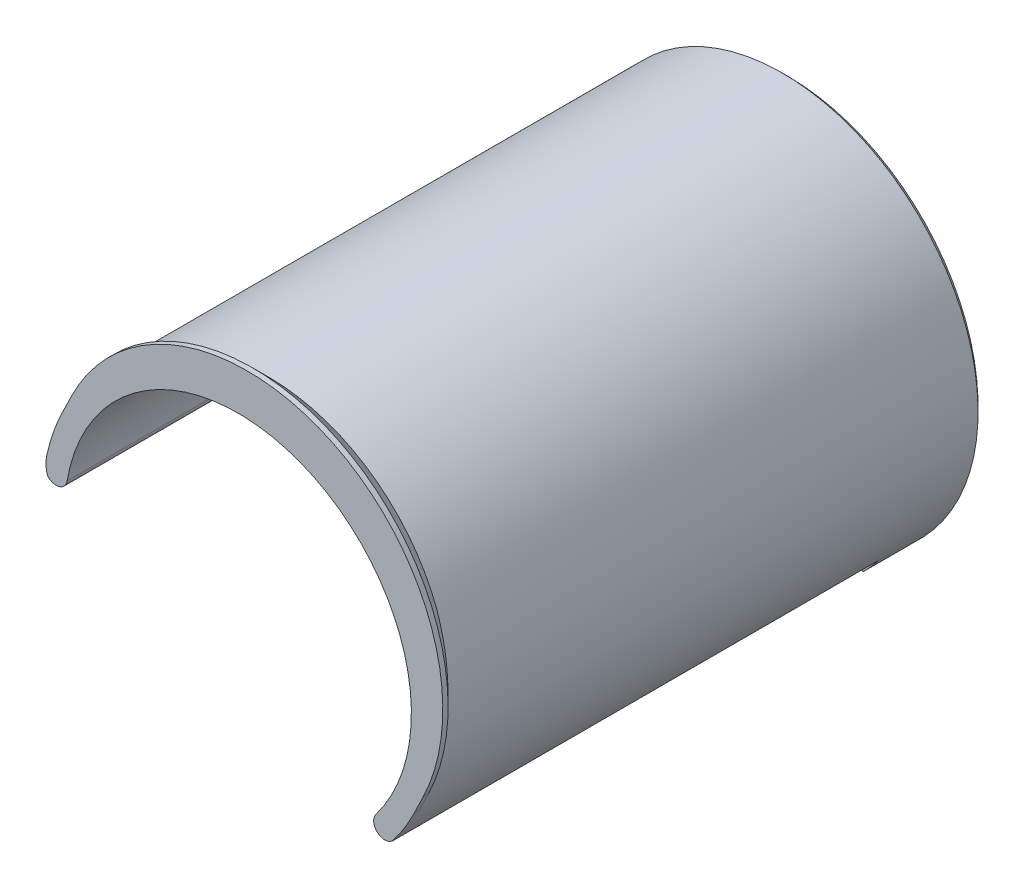
SolidWorks part; units mm, degrees
ref_plane "Front Plane" through (0, 0, 0) normal (0, 0, 1) x (1, 0, 0)
ref_plane "Top Plane" through (0, 0, 0) normal (0, 1, 0) x (1, 0, 0)
ref_plane "Right Plane" through (0, 0, 0) normal (1, 0, 0) x (0, 0, -1)
sketch "Sketch1" plane through (0, 0, 0) normal (0, 0, 1) x (1, 0, 0)
  line L0 (0, 0) -> (2.4655, -2.0399) construction
  line L1 (0, -72.4563) -> (0, 0) construction
  line L2 (-24.9525, 0) -> (63.5919, 0) construction
  line L5 (-4.4616, 0) -> (-3.2, 0)
  line L7 (2.4655, -2.0399) -> (17.7098, -14.6529)
  arc A0 (21.6843, -14.7364) -> (-7.5908, 3.8693) centre (10.5, 0) ccw
  arc A1 (-3.2, 0) -> (2.4655, -2.0399) centre (0, 0) ccw
  arc A2 (17.7098, -14.6529) -> (21.6843, -14.7364) centre (19.7497, -12.1874) ccw
  circle A3 centre (19.7497, -12.1874) radius 1.6
  arc A4 (-4.4616, 0) -> (-7.5908, 3.8693) centre (-4.4616, 3.2) cw
  circle A9 centre (0, 0) radius 1.6
  dimension "D1" = 3.2
  dimension "D3" = 10.5
  dimension "D5" = 3.2
  dimension "D6" = 37
  dimension "D7" = 39.604
extrude "Boss-Extrude1" add sketch "Sketch1" along normal blind 52
sketch "Sketch2" plane through (0, 0, 52) normal (0, 0, 1) x (1, 0, 0)
  line L0 (-7.7522, 2.9303) -> (-10.2673, 3.3341)
  line L1 (25.098, -11.3414) -> (27.1096, -12.9043)
  arc A0 (23.5461, -9.9377) -> (-5.6671, 2.754) centre (10.5, 0) ccw
  arc A1 (21.6843, -14.7364) -> (-7.5908, 3.8693) centre (10.5, 0) ccw construction
  arc A2 (23.5461, -9.9377) -> (25.098, -11.3414) centre (24.3814, -10.574) ccw
  arc A3 (-7.7522, 2.9303) -> (-5.6671, 2.754) centre (-6.7022, 2.9303) ccw
  arc A4 (-7.7522, 2.9303) -> (25.098, -11.3414) centre (10.5, 0) ccw construction
  arc A5 (-10.2673, 3.3341) -> (27.1096, -12.9043) centre (10.5, 0) ccw
  dimension "D1" = 2.1
extrude "Cut-Extrude1" cut sketch "Sketch2" against normal offset from surface (46 mm away) 6 up to face at (21.3497, -12.1874, 0)
sketch "Sketch3" plane through (0, 0, 6) normal (0, 0, 1) x (1, 0, 0)
  line L0 (1.6921, 2.716) -> (20.4366, -8.962)
  arc A1 (1.6921, 2.716) -> (-0.5483, 3.1527) centre (0, 0) ccw
  circle A2 centre (19.7497, -12.1874) radius 3.2 construction
  arc A3 (-3.908, 7.8339) -> (-0.5483, 3.1527) centre (-1.0967, 6.3053) ccw
  arc A4 (20.4366, -8.962) -> (24.9478, -7.7602) centre (22.1287, -6.246) ccw
  arc A6 (24.9478, -7.7602) -> (-3.908, 7.8339) centre (10.5, 0) ccw
extrude "Cut-Extrude2" cut sketch "Sketch3" against normal offset from surface (3.6 mm away) 2.4 up to face at (21.3497, -12.1874, 0)
chamfer "Chamfer1" distance 3 angle 45 5 edges at (18.2971, 14.428, 2.4) (22.9525, -9.3381, 2.4) (11.0644, -3.123, 2.4) (0.6121, 3.1409, 2.4) (-3.6964, 4.4395, 2.4)
chamfer "Chamfer2" distance 0.5 angle 45 8 edges at (1.6, 0, 0) (-3.8308, 0, 0) (-1.0841, -3.0108, 0) (10.0877, -8.3464, 0) (19.6825, -15.3867, 0) (20.4231, 15.6135, 0) (-6.9498, 1.1877, 0) (21.3497, -12.1874, 0)
sketch "Sketch4" plane through (0, 0, 52) normal (0, 0, 1) x (1, 0, 0)
  line L0 (-6.1477, 8.0687) -> (-5.2754, 9.8684)
  line L1 (27.1477, -8.0687) -> (28.02, -6.2689)
  line L2 (-6.1477, 8.0687) -> (-4.258, 7.1528)
  line L3 (25.258, -7.1528) -> (27.1477, -8.0687)
  arc A0 (28.02, -6.2689) -> (-5.2754, 9.8684) centre (11.3723, 1.7998) ccw
  arc A1 (25.1091, -11.3501) -> (-7.5908, 3.8693) centre (10.5, 0) ccw construction
  arc A2 (25.258, -7.1528) -> (-4.258, 7.1528) centre (10.5, 0) ccw
  arc A3 (24.9478, -7.7602) -> (-3.908, 7.8339) centre (10.5, 0) ccw construction
  dimension "D1" = 2
extrude "Boss-Extrude2" add sketch "Sketch4" against normal blind 2
chamfer "Chamfer3" distance 1.5 angle 45 3 edges at (27.5839, -7.1688, 50) (-5.7116, 8.9686, 50) (19.441, 18.4475, 50)
sketch "Sketch5" plane through (0, 0, 6) normal (0, 0, 1) x (1, 0, 0)
  line L0 (-3.2, 0) -> (-4.4616, 0) construction
  line L1 (3.3486, 0) -> (1.6743, 2.9)
  line L2 (1.6743, 2.9) -> (-1.6743, 2.9)
  line L3 (-1.6743, 2.9) -> (-5.4802, -3.6919)
  line L4 (-3.3486, 0) -> (-1.6743, -2.9) construction
  line L5 (-1.6743, -2.9) -> (1.6743, -2.9) construction
  line L6 (0.1067, -5.6153) -> (3.3486, 0)
  line L8 (18.0754, -9.2874) -> (13.043, -18.0037)
  line L9 (16.4011, -12.1874) -> (18.0754, -15.0874) construction
  line L10 (18.0754, -15.0874) -> (21.4241, -15.0874) construction
  line L11 (21.4241, -15.0874) -> (23.0984, -12.1874) construction
  line L12 (26.4564, -18.0037) -> (21.4241, -9.2874)
  line L13 (21.4241, -9.2874) -> (18.0754, -9.2874)
  line L14 (13.043, -18.0037) -> (26.4564, -18.0037)
  line L15 (-5.4802, -3.6919) -> (0.1067, -5.6153)
  circle A0 centre (0, 0) radius 2.9 construction
  circle A1 centre (19.7497, -12.1874) radius 2.9 construction
  dimension "D1" = 5.8
extrude "Cut-Extrude4" cut sketch "Sketch5" against normal blind 2.5
